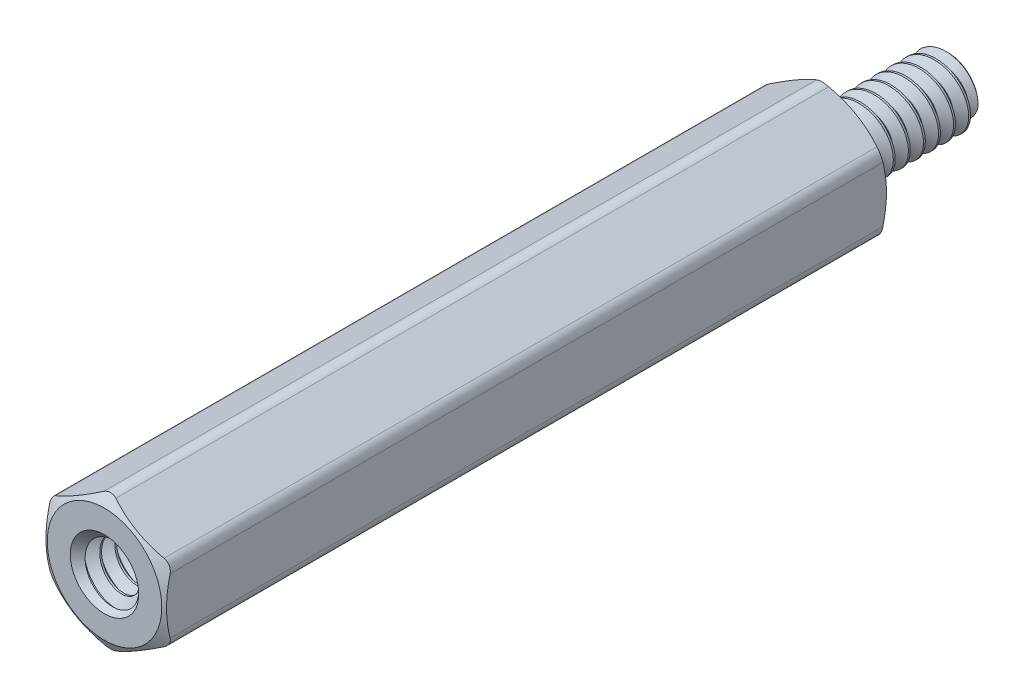
SolidWorks part; units mm, degrees
ref_plane "Front Plane" through (0, 0, 0) normal (0, 0, 1) x (1, 0, 0)
ref_plane "Top Plane" through (0, 0, 0) normal (0, 1, 0) x (1, 0, 0)
ref_plane "Right Plane" through (0, 0, 0) normal (1, 0, 0) x (0, 0, -1)
sketch "Sketch1" plane through (0, 0, 0) normal (0, 0, 1) x (1, 0, 0)
  line L1 (3.175, 1.8331) -> (0, 3.6662)
  line L2 (0, 3.6662) -> (-3.175, 1.8331)
  line L3 (-3.175, 1.8331) -> (-3.175, -1.8331)
  line L4 (-3.175, -1.8331) -> (0, -3.6662)
  line L5 (0, -3.6662) -> (3.175, -1.8331)
  line L6 (3.175, -1.8331) -> (3.175, 1.8331)
  circle A0 centre (0, 0) radius 3.175 construction
  point P10 (0, -3.175)
  dimension "Hex Size" = 6.35
sketch "Sketch2" plane through (0, 0, 0) normal (1, 0, 0) x (0, 0, -1)
  line L0 (6.35, 0) -> (-38.1, 0) construction
  line L2 (0, 1.7526) -> (0, -1.7526) construction
  line L3 (-28.575, 1.7526) -> (-28.575, -1.7526) construction
  line L4 (-38.8441, 1.8385) -> (-38.4473, 1.1511) construction
  line L5 (-38.4473, 1.1511) -> (-38.0504, 1.8385) construction
  line L6 (-38.0504, 1.8385) -> (-38.8441, 1.8385) construction
  line L7 (-38.7945, 1.7526) -> (-38.1, 1.7526) construction
  line L8 (-38.4969, 1.237) -> (-38.3977, 1.237) construction
  line L9 (-38.4473, 1.237) -> (-38.4473, 1.1511) construction
  line L10 (-38.4473, 1.7526) -> (-38.4473, 1.8385) construction
  line L11 (6.3004, 1.8385) -> (7.0941, 1.8385) construction
  line L12 (7.0941, 1.8385) -> (6.6973, 1.1511) construction
  line L13 (6.6973, 1.1511) -> (6.3004, 1.8385) construction
  line L14 (6.35, 1.7526) -> (7.0445, 1.7526) construction
  line L15 (6.6477, 1.237) -> (6.7469, 1.237) construction
  line L16 (6.6973, 1.237) -> (6.6973, 1.1511) construction
  line L17 (6.6973, 1.7526) -> (6.6973, 1.8385) construction
  line L18 (0, 3.6662) -> (-38.1, 3.6662) construction
  point P6 (0, 0)
  point P9 (-28.575, 0)
  dimension "Length" = 38.1
sketch "Sketch3" plane through (0, 0, 0) normal (1, 0, 0) x (0, 0, -1)
  line L0 (-28.575, 0) -> (6.35, 0)
  line L1 (-28.575, 1.7526) -> (-28.575, -1.7526) construction
  line L2 (6.35, 0) -> (6.35, 1.5542)
  line L3 (6.35, 1.5542) -> (6.1516, 1.7526)
  line L4 (6.1516, 1.7526) -> (1.0597, 1.7526)
  line L5 (1.0597, 1.7526) -> (0.762, 1.237)
  line L6 (-28.575, 0) -> (-28.575, 1.5542)
  line L7 (-28.575, 1.5542) -> (-28.7734, 1.7526)
  line L8 (-28.7734, 1.7526) -> (-37.9016, 1.7526)
  line L9 (-37.9016, 1.7526) -> (-38.1, 1.951)
  line L10 (6.1516, 0) -> (6.1516, -1.7526) construction
  line L11 (-38.1, 1.951) -> (-38.1, 3.175)
  line L12 (-38.1, 3.175) -> (0, 3.175)
  line L14 (0.762, 1.237) -> (0.1984, 1.237)
  line L15 (0, 1.4355) -> (0, 3.175)
  arc A0 (0, 1.4355) -> (0.1984, 1.237) centre (0.1984, 1.4355) ccw
  point P5 (-38.1, -3.175)
  point P8 (-36.1156, -1.7526)
  point P9 (4.3656, -1.7526)
  point P27 (0, 1.237)
  dimension "D4" = 0.1984
  dimension "D2" = 0.1984
  dimension "D1" = 45
  dimension "D6" = 1.9844
  dimension "D7" = 60
  dimension "D3" = 1.9844
  dimension "D5" = 0.762
revolve "Revolve1" add sketch "Sketch3" angle 360 about L0
sketch "Sketch4" plane through (0, 0, 38.1) normal (0, 0, 1) x (1, 0, 0)
  line L0 (0, 3.175) -> (0, 1.7526) construction
  line L1 (-3.175, 1.8331) -> (-3.175, -1.8331)
  line L2 (-3.175, -1.8331) -> (0, -3.6662)
  line L3 (0, -3.6662) -> (3.175, -1.8331)
  line L4 (3.175, -1.8331) -> (3.175, 1.8331)
  line L5 (3.175, 1.8331) -> (0, 3.6662)
  line L6 (0, 3.6662) -> (-3.175, 1.8331)
  circle A0 centre (0, 0) radius 3.175 construction
  circle A1 centre (0, 0) radius 2.4638
  circle A2 centre (0, 0) radius 3.175 construction
  point P16 (0, 2.4638)
extrude "Boss-Extrude1" add sketch "Sketch4" against normal up to surface (38.1 mm away) up to face at (0, 3.175, 0)
sketch "Sketch5" plane through (0, 0, 38.1) normal (0, 0, 1) x (1, 0, 0)
  line L0 (-1.0053, 1.4356) -> (1.0053, -1.4356) construction
  line L1 (0, 1.7526) -> (0, -1.7526) construction
  line L3 (0, -3.9247) -> (0, 3.9247) construction
  circle A0 centre (0, 0) radius 3.0162
  point P11 (1.0053, -1.4356)
  dimension "D1" = 6.0325
  dimension "D2" = 35
extrude "Cut-Extrude1" cut sketch "Sketch5" against normal through all draft 60 flip side to cut
sketch "Sketch6" plane through (0, 0, 0) normal (0, 0, -1) x (-1, 0, 0)
  circle A0 centre (0, 0) radius 3.0162
  circle A1 centre (0, 0) radius 3.0162 construction
extrude "Cut-Extrude2" cut sketch "Sketch6" against normal through all draft 60 flip side to cut
fillet "Fillet1" radius 0.635 6 edges at (0, 3.6662, 19.05) (-3.175, -1.8331, 19.05) (0, -3.6662, 19.05) (3.175, -1.8331, 19.05) (3.175, 1.8331, 19.05) (-3.175, 1.8331, 19.05)
sketch "Drawing1" plane through (0, 0, 0) normal (1, 0, 0) x (0, 0, -1)
  line L0 (-38.1, 1.7526) -> (-28.575, 1.7526) construction
  line L1 (-28.575, 1.7526) -> (-28.575, -1.7526) construction
  line L2 (-28.575, -1.7526) -> (-38.1, -1.7526) construction
sketch "Sketch7" plane through (0, 0, 0) normal (-1, 0, 0) x (0, 0, 1)
  line L0 (-6.6477, 1.237) -> (-6.7469, 1.237)
  line L1 (-6.7469, 1.237) -> (-7.0693, 1.7956)
  line L2 (-7.0941, 1.8385) -> (-6.6973, 1.1511) construction
  line L3 (-7.0693, 1.7956) -> (-6.3252, 1.7956)
  line L4 (-6.6973, 1.1511) -> (-6.3004, 1.8385) construction
  line L5 (-6.3252, 1.7956) -> (-6.6477, 1.237)
  line L6 (-6.6973, 1.7526) -> (-6.6973, 1.8385) construction
  point P12 (-6.6973, 1.7956)
sketch "Sketch8" plane through (0, 0, -6.35) normal (0, 0, -1) x (-1, 0, 0)
  circle A0 centre (0, 0) radius 1.7526
curve "Helix/Spiral1" pitch 0.7937 height 6.1595 turns 7.76
sweep "Cut-Sweep1" cut profiles "Sketch7" path "Helix/Spiral1"
sketch "Sketch9" plane through (0, 0, 28.575) normal (0, 0, 1) x (1, 0, 0)
  circle A0 centre (0, 0) radius 1.951
extrude "Boss-Extrude2" add sketch "Sketch9" along normal up to surface (9.525 mm away)
sketch "Sketch10" plane through (0, 0, 0) normal (1, 0, 0) x (0, 0, -1)
  line L0 (6.35, 0) -> (-38.1, 0) construction
  line L1 (-28.575, 1.7526) -> (-38.1, 1.7526)
  line L2 (-28.575, 1.7526) -> (-28.575, 0)
  line L3 (-28.575, 0) -> (-38.1, 0)
  line L4 (-38.1, 1.7526) -> (-38.1, 0)
revolve "Revolve2" add sketch "Sketch10" angle 360 about L0
sketch "Sketch11" plane through (0, 0, 38.1) normal (0, 0, 1) x (1, 0, 0)
  circle A0 centre (0, 0) radius 1.7526
  circle A1 centre (0, 0) radius 1.7526 construction
sketch "Sketch12" plane through (0, 0, 0) normal (1, 0, 0) x (0, 0, -1)
  line L0 (-38.4969, 1.237) -> (-38.3977, 1.237)
  line L1 (-38.3977, 1.237) -> (-38.0752, 1.7956)
  line L2 (-38.4473, 1.1511) -> (-38.0504, 1.8385) construction
  line L3 (-38.0752, 1.7956) -> (-38.8193, 1.7956)
  line L4 (-38.8441, 1.8385) -> (-38.4473, 1.1511) construction
  line L5 (-38.8193, 1.7956) -> (-38.4969, 1.237)
  line L6 (-38.4473, 1.7526) -> (-38.4473, 1.8385) construction
  point P12 (-38.4473, 1.7956)
curve "Helix/Spiral2" pitch 0.7937 height 10.3187 turns 13
sweep "Cut-Sweep2" cut profiles "Sketch12" path "Helix/Spiral2"
combine bodies "Combine1" operation type subtract main body 113 bodies to subtract 114
sketch "Sketch13" plane through (0, 0, 38.1) normal (0, 0, 1) x (1, 0, 0)
  circle A0 centre (0, 0) radius 1.8034
  dimension "D1" = 0.0508
extrude "Cut-Extrude3" cut sketch "Sketch13" against normal through all draft 45
equation "\"Thread Pitch (B)/8@Sketch2\"=\"Thread Pitch (B)@Sketch2\"/8"
equation "\"Thread Pitch (A)/8@Sketch2\"=\"Thread Pitch (A)@Sketch2\"/8"
equation "\"D1@Sketch5\" = \"Hex Size@Sketch1\" * .95"
equation "\"D1@Fillet1\" = \"Hex Size@Sketch1\" * .1"
equation "\"D2@Sketch3\" = \"Thread Pitch (A)@Sketch2\" * .25"
equation "\"D4@Sketch3\" = \"D2@Sketch3\""
equation "\"D6@Sketch3\" = \"Thread Pitch (A)@Sketch2\" * 2.5"
equation "\"D3@Helix/Spiral1\" = \"Thread Length (A)@Sketch2\" - \"D5@Sketch3\" * .25"
equation "\"D4@Helix/Spiral1\" = \"Thread Pitch (A)@Sketch2\""
equation "\"D3@Sketch3\" = \"Thread Pitch (B)@Sketch2\" * 2.5"
equation "\"D5@Sketch3\" = \"Thread Length (A)@Sketch2\" * .12"
equation "\"D3@Helix/Spiral2\" = \"Minimum Thread Length (B)@Sketch2\" + \"Thread Pitch (B)@Sketch2\""
equation "\"D4@Helix/Spiral2\" = \"Thread Pitch (B)@Sketch2\""
